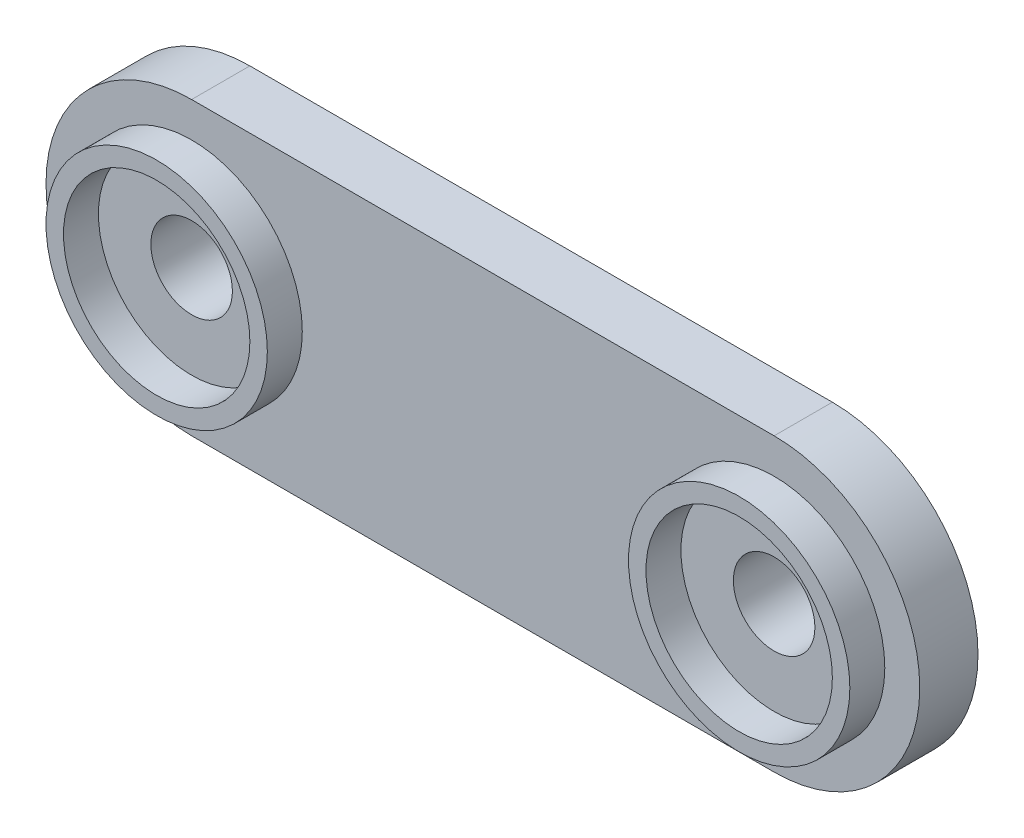
SolidWorks part; units mm, degrees
ref_plane "Front Plane" through (0, 0, 0) normal (0, 0, 1) x (1, 0, 0)
ref_plane "Top Plane" through (0, 0, 0) normal (0, 1, 0) x (1, 0, 0)
ref_plane "Right Plane" through (0, 0, 0) normal (1, 0, 0) x (0, 0, -1)
sketch "Sketch1" plane through (0, 0, 0) normal (0, 0, 1) x (1, 0, 0)
  line L1 (0, 0) -> (50, 0)
  line L2 (0, 0) -> (0, 25)
  line L3 (0, 25) -> (50, 25)
  line L4 (50, 0) -> (50, 25)
  line L5 (50, 15) -> (50, 10)
  circle A0 centre (0, 12.5) radius 12.5
  circle A4 centre (50, 12.5) radius 12.5
  dimension "D1" = 25
  dimension "D4" = 50
extrude "Boss-Extrude2" add sketch "Sketch1" along normal blind 5 contours L2 L1 L4 L3 | A0 | A4
sketch "Sketch3" plane through (0, 0, 5) normal (0, 0, 1) x (1, 0, 0)
  line L0 (0, 0) -> (50, 0) construction
  line L1 (0, 25) -> (50, 25) construction
  line L2 (0, 0) -> (50, 0) construction
  line L3 (0, 25) -> (50, 25) construction
  arc A0 (50, 0) -> (50, 25) centre (50, 12.5) ccw construction
  arc A1 (0, 25) -> (0, 0) centre (0, 12.5) ccw construction
  arc A2 (50, 0) -> (50, 25) centre (50, 12.5) ccw construction
  arc A3 (0, 25) -> (0, 0) centre (0, 12.5) ccw construction
  circle A4 centre (0, 12.5) radius 3.5
  circle A5 centre (50, 12.5) radius 3.5
  circle A6 centre (0, 12.5) radius 8
  circle A7 centre (0, 12.5) radius 9.5
  circle A8 centre (50, 12.5) radius 8
  circle A9 centre (50, 12.5) radius 9.5
  dimension "D1" = 7
  dimension "D2" = 7
  dimension "D3" = 16
  dimension "D4" = 19
  dimension "D5" = 16
  dimension "D6" = 19
extrude "Cut-Extrude3" cut sketch "Sketch3" against normal up to next contours A4 | A5
extrude "Boss-Extrude3" add sketch "Sketch3<3>" along normal blind 3 contours A7 A6 | A9 A8 region at (-9.2313, 12.5, 5) region at (40.7687, 12.5, 5)
sketch "Sketch3<3>" plane through (0, 0, 5) normal (0, 0, 1) x (1, 0, 0) same geometry as "Sketch3"
equation "\"LinkMiddle_Length\"=50"
equation "\"D4@Sketch1\"=\"LinkMiddle_Length\""
